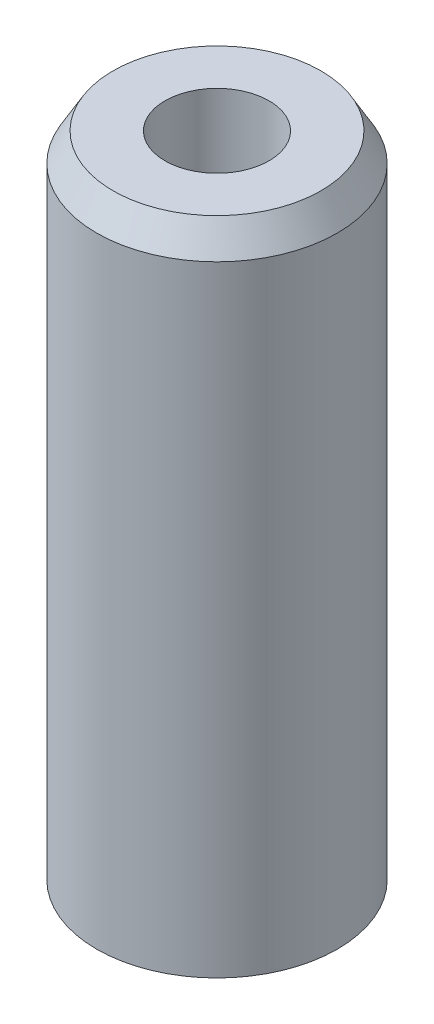
SolidWorks part; units mm, degrees
ref_plane "Front Plane" through (0, 0, 0) normal (0, 0, 1) x (1, 0, 0)
ref_plane "Top Plane" through (0, 0, 0) normal (0, 1, 0) x (1, 0, 0)
ref_plane "Right Plane" through (0, 0, 0) normal (1, 0, 0) x (0, 0, -1)
sketch "Sketch1" plane through (0, 0, 0) normal (0, 1, 0) x (1, 0, 0)
  circle A0 centre (0, 0) radius 10
  dimension "SHAFT_OD" = 20
extrude "Boss-Extrude1" add sketch "Sketch1" along normal blind 55.2616
sketch "Sketch2" plane through (0, 0, 0) normal (0, 1, 0) x (1, 0, 0)
  circle A0 centre (0, 0) radius 4.324
  dimension "BORE_D" = 8.648
extrude "Cut-Extrude1" cut sketch "Sketch2" along normal through all
chamfer "Chamfer1" distance 2.3597 angle 30 2 edges at (0, 55.2616, 10) (0, 0, 10) first distance on face at (0, 55.2616, 10) first distance on face at (0, 0, 4.324)
